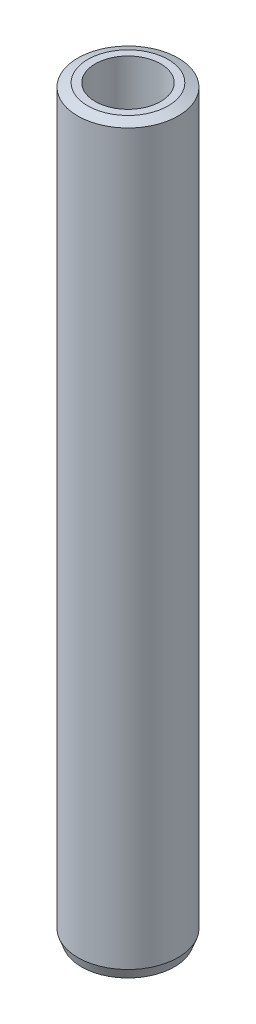
SolidWorks part; units mm, degrees
ref_plane "Front Plane" through (0, 0, 0) normal (0, 0, 1) x (1, 0, 0)
ref_plane "Top Plane" through (0, 0, 0) normal (0, 1, 0) x (1, 0, 0)
ref_plane "Right Plane" through (0, 0, 0) normal (1, 0, 0) x (0, 0, -1)
sketch "Sketch1" plane through (0, 0, 0) normal (0, 1, 0) x (1, 0, 0)
  circle A0 centre (0, 0) radius 12.5
  dimension "SHAFT_OD" = 25
extrude "Boss-Extrude1" add sketch "Sketch1" along normal blind 184.7891
sketch "Sketch2" plane through (0, 0, 0) normal (0, 1, 0) x (1, 0, 0)
  circle A0 centre (0, 0) radius 8.1397
  dimension "BORE_D" = 16.2794
extrude "Cut-Extrude1" cut sketch "Sketch2" along normal through all
chamfer "Chamfer1" distance 0.9358 angle 69.412 2 edges at (0, 184.7891, 12.5) (0, 0, 12.5) first distance on face at (0, 184.7891, 12.5) first distance on face at (0, 0, 8.1397)
